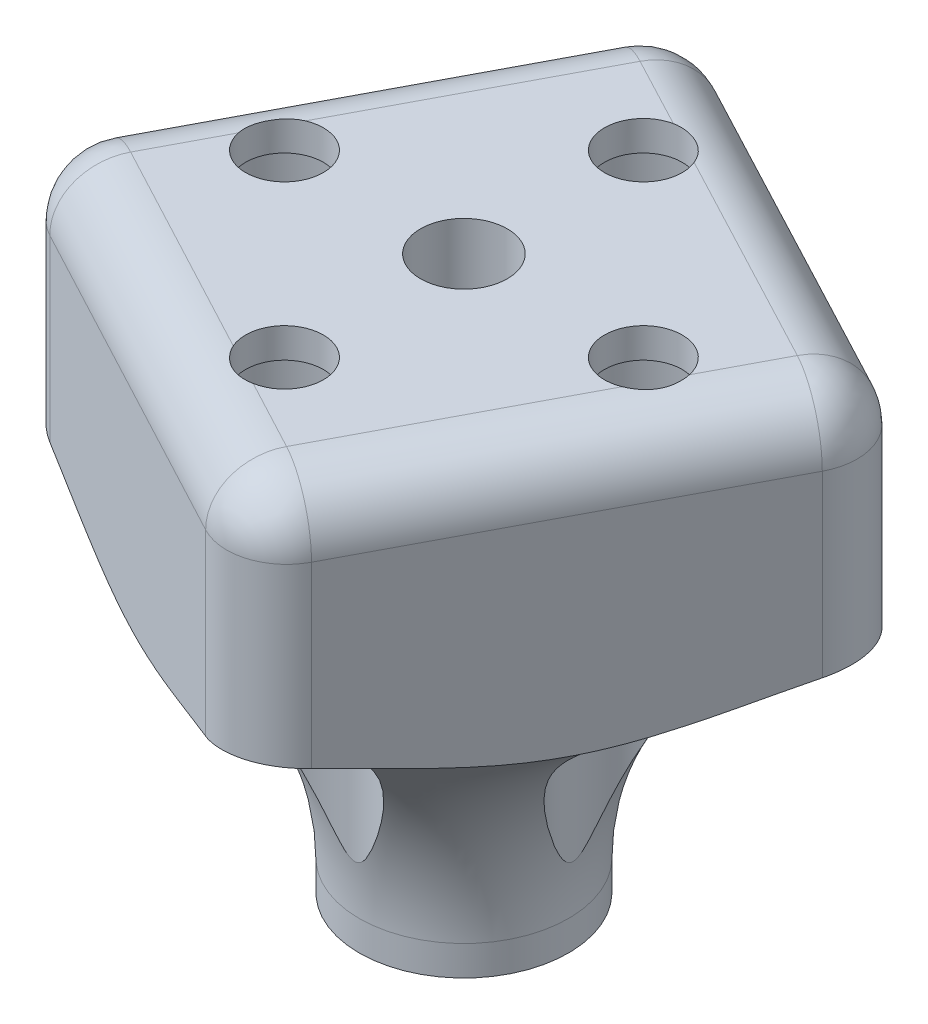
SolidWorks part; units mm, degrees
ref_plane "Alzado" through (0, 0, 0) normal (0, 0, 1) x (1, 0, 0)
ref_plane "Planta" through (0, 0, 0) normal (0, 1, 0) x (1, 0, 0)
ref_plane "Vista lateral" through (0, 0, 0) normal (1, 0, 0) x (0, 0, -1)
sketch "Croquis1" plane through (0, 0, 0) normal (0, 1, 0) x (1, 0, 0)
  circle A0 centre (0, 0) radius 3.5
  dimension "D1" = 7
extrude "Saliente-Extruir1" add sketch "Croquis1" along normal blind 10 and the other way blind 1
sketch "Croquis2" plane through (0, -1, 0) normal (0, -1, 0) x (1, 0, 0)
  line L0 (-1.325, 1.4981) -> (1.325, 1.4981)
  arc A0 (-1.325, 1.4981) -> (1.325, 1.4981) centre (0, 0) ccw
  dimension "D1" = 1.4981
  dimension "D2" = 2
extrude "Cortar-Extruir2" cut sketch "Croquis2" against normal blind 7.6
sketch "Croquis4" plane through (0, 10, 0) normal (0, 1, 0) x (1, 0, 0)
  circle A0 centre (0, 0) radius 2
  dimension "D1" = 4
extrude "Cortar-Extruir4" cut sketch "Croquis4" against normal blind 3.4 contours A0
ref_plane "Plano2" through (0, 10, 0) normal (0, 1, 0) x (1, 0, 0)
sketch "Croquis5" plane through (0, 10, 0) normal (0, 1, 0) x (1, 0, 0)
  circle A0 centre (0, 0) radius 12.5
  dimension "D1" = 25
extrude "Saliente-Extruir2" add sketch "Croquis5" along normal blind 7.5
sketch "Croquis6" plane through (0, 17.5, 0) normal (0, 1, 0) x (1, 0, 0)
  line L0 (0, 0) -> (-7.3361, 0) construction
  line L1 (0, 0) -> (0, -6) construction
  circle A0 centre (0, -6) radius 1.3
  circle A1 centre (-6, 0) radius 1.3
  circle A2 centre (0, 6) radius 1.3
  circle A3 centre (6, 0) radius 1.3
  point P14 (0, 0)
  dimension "D1" = 2.6
  dimension "D2" = 6
  dimension "D3" = 90
  dimension "D4" = 4
extrude "Cortar-Extruir5" cut sketch "Croquis6" against normal through all
sketch "Croquis7" plane through (0, 17.5, 0) normal (0, 1, 0) x (1, 0, 0)
  circle A0 centre (0, 0) radius 1.45
  dimension "D1" = 2.9
extrude "Cortar-Extruir6" cut sketch "Croquis7" against normal through all
sketch "Croquis8" plane through (0, 17.5, 0) normal (0, 1, 0) x (1, 0, 0)
  line L0 (3.447, -11.2534) -> (11.2229, 3.4631)
  line L1 (11.2229, 3.4631) -> (-3.4631, 11.2229)
  line L2 (-3.4631, 11.2229) -> (-11.2182, -3.4543)
  line L3 (-11.2182, -3.4543) -> (3.447, -11.2534)
  circle A0 centre (-6, 0) radius 1.3 construction
  circle A1 centre (0, 6) radius 1.3 construction
  circle A2 centre (0, 0) radius 13
  circle A3 centre (6, 0) radius 1.3 construction
  circle A4 centre (0, 0) radius 2 construction
  dimension "D3" = 5.5
  dimension "D4" = 3
  dimension "D5" = 3
  dimension "D6" = 3
  dimension "D7" = 11
  dimension "D1" = 16.6
  dimension "D2" = 16.61
extrude "Cortar-Extruir10" cut sketch "Croquis8" against normal through all
sketch "Croquis13" plane through (0, 10, 0) normal (0, -1, 0) x (-1, 0, 0)
  circle A0 centre (6, 0) radius 2.35
  circle A1 centre (0, -6) radius 2.35
  circle A2 centre (-6, 0) radius 2.35
  circle A3 centre (0, 6) radius 2.35
  point P12 (0, 0)
  dimension "D1" = 4.7
  dimension "D2" = 4
extrude "Cortar-Extruir13" cut sketch "Croquis13" against normal blind 6.5
fillet "Redondeo2" radius 10 1 edges at (0, 10, 3.5)
fillet "Redondeo3" radius 2 8 edges at (11.2229, 13.6724, -3.4631) (3.447, 13.6746, 11.2534) (-11.2182, 13.6718, 3.4543) (-3.4631, 13.6724, -11.2229) (-3.8856, 17.5, 7.3539) (7.3349, 17.5, 3.8951) (3.8799, 17.5, -7.343) (-7.3407, 17.5, -3.8843)
